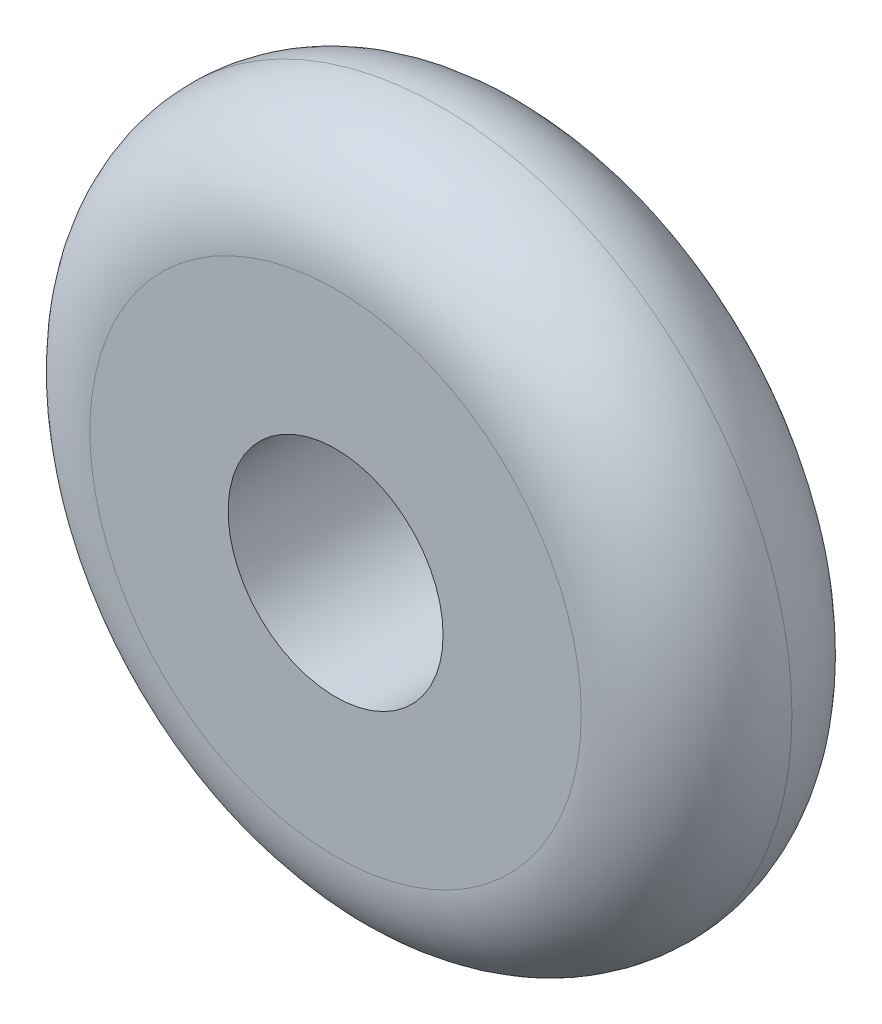
SolidWorks part; units mm, degrees
ref_plane "Plan de face" through (0, 0, 0) normal (0, 0, 1) x (1, 0, 0)
ref_plane "Plan de dessus" through (0, 0, 0) normal (0, 1, 0) x (1, 0, 0)
ref_plane "Plan de droite" through (0, 0, 0) normal (1, 0, 0) x (0, 0, -1)
sketch "Esquisse1" plane through (0, 0, 0) normal (0, 0, 1) x (1, 0, 0)
  circle A0 centre (0, 0) radius 40
  circle A1 centre (0, 0) radius 12.25
  dimension "D1" = 80
  dimension "D2" = 24.5
extrude "Boss.-Extru.1" add sketch "Esquisse1" along normal blind 24
fillet "Congé1" radius 12 2 edges at (40, 0, 0) (40, 0, 24)
